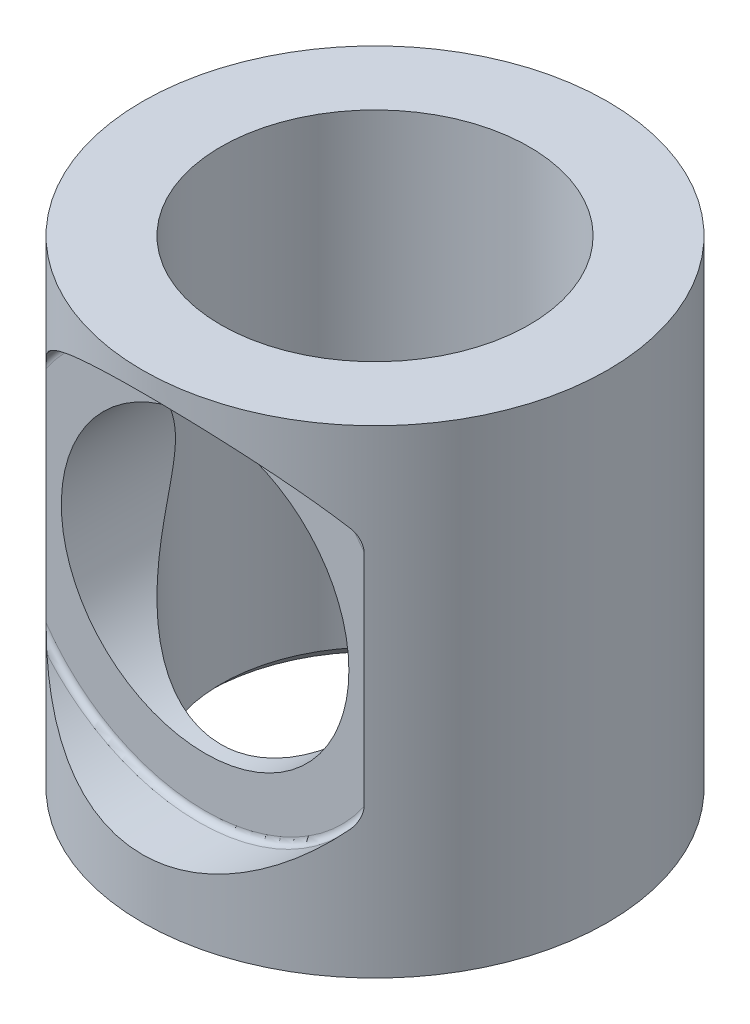
SolidWorks part; units mm, degrees
material "PTFE (general)"
ref_plane "Front Plane" through (0, 0, 0) normal (0, 0, 1) x (1, 0, 0)
ref_plane "Top Plane" through (0, 0, 0) normal (0, 1, 0) x (1, 0, 0)
ref_plane "Right Plane" through (0, 0, 0) normal (1, 0, 0) x (0, 0, -1)
sketch "Sketch1" plane through (0, 0, 0) normal (0, 1, 0) x (1, 0, 0)
  circle A0 centre (0, 0) radius 8.9
  circle A1 centre (0, 0) radius 5.9
  dimension "D1" = 17.8
  dimension "D2" = 11.8
extrude "Boss-Extrude1" add sketch "Sketch1" against normal blind 18.3
sketch "Sketch3" plane through (0, 0, 0) normal (0, 0, 1) x (1, 0, 0)
  line L1 (5.9, 0) -> (-5.9, 0) construction
  circle A0 centre (0, -8.4) radius 7.65
  dimension "D1" = 15.3
  dimension "D2" = 8.4
extrude "Cut-Extrude5" cut sketch "Sketch3" along normal through all from offset 6.5
sketch "Sketch6" plane through (0, 0, 6.5) normal (0, 0, 1) x (1, 0, 0)
  circle A0 centre (0, -8.4) radius 5.5
  dimension "D1" = 11
extrude "Cut-Extrude6" cut sketch "Sketch6" against normal blind 7 and the other way through all
chamfer "Chamfer1" distance 0.5 angle 45 1 edges at (0, -18.3, 5.9)
fillet "Fillet1" radius 0.25 2 edges at (0, -0.75, 6.5) (0, -16.05, 6.5)
